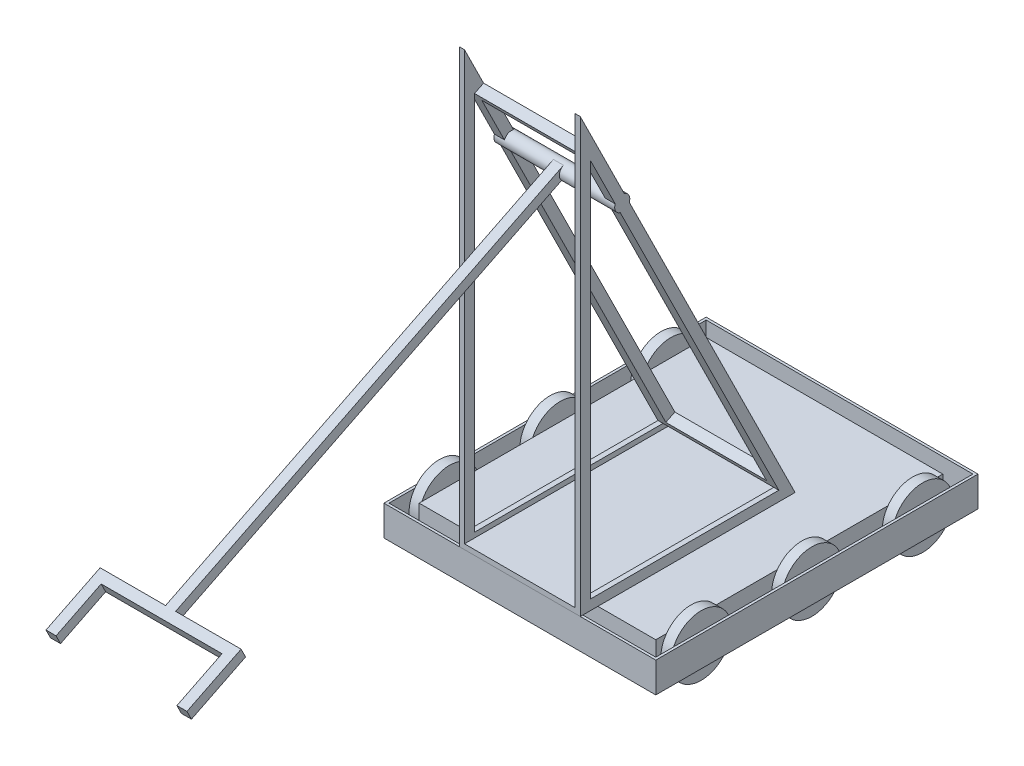
SolidWorks part; units mm, degrees
ref_plane "Front Plane" through (0, 0, 0) normal (0, 0, 1) x (1, 0, 0)
ref_plane "Top Plane" through (0, 0, 0) normal (0, 1, 0) x (1, 0, 0)
ref_plane "Right Plane" through (0, 0, 0) normal (1, 0, 0) x (0, 0, -1)
sketch "Sketch3" plane through (0, 0, 0) normal (0, 1, 0) x (1, 0, 0)
  line L5 (-342.9, -406.4) -> (342.9, -406.4)
  line L6 (-342.9, -406.4) -> (-342.9, 406.4)
  line L7 (-342.9, 406.4) -> (342.9, 406.4)
  line L8 (342.9, -406.4) -> (342.9, 406.4)
  line L9 (-342.9, -406.4) -> (342.9, 406.4) construction
  line L10 (-342.9, 406.4) -> (342.9, -406.4) construction
  point P0 (0, 0)
  dimension "D1" = 812.8
  dimension "D2" = 685.8
extrude "Extrude-Thin1" add sketch "Sketch3" along normal blind 76.2 thin contours L6 L7 L8 L5 thin type one direction reverse wall 6.35
sketch "Sketch5" plane through (0, 0, 0) normal (0, 1, 0) x (1, 0, 0)
  line L8 (-292.1, -355.6) -> (292.1, -355.6)
  line L9 (292.1, -355.6) -> (292.1, 355.6)
  line L10 (292.1, 355.6) -> (-292.1, 355.6)
  line L11 (-292.1, 355.6) -> (-292.1, -355.6)
  line L12 (-292.1, -355.6) -> (292.1, -355.6)
  line L13 (292.1, -355.6) -> (292.1, 355.6)
  line L14 (292.1, 355.6) -> (-292.1, 355.6)
  line L15 (-292.1, 355.6) -> (-292.1, -355.6)
  dimension "D1" = 50.8
extrude "Extrude-Thin2" add sketch "Sketch5" along normal blind 76.2 separate body thin thin type one direction wall 6.35
sketch "Sketch6" plane through (-292.1, 0, 0) normal (1, 0, 0) x (0, 0, -1)
  line L0 (0, 83.82) -> (0, -83.82) construction
  line L1 (0, 76.2) -> (0, 0) construction
  line L2 (355.6, 76.2) -> (-355.6, 76.2) construction
  line L3 (355.6, 0) -> (-355.6, 0) construction
  circle A0 centre (0, 38.1) radius 76.2
  circle A1 centre (-279.4, 38.1) radius 76.2
  circle A2 centre (279.4, 38.1) radius 76.2
  dimension "D1" = 152.4
  dimension "D2" = 152.4
  dimension "D5" = 152.4
  dimension "D3" = 279.4
  dimension "D4" = 279.4
extrude "Boss-Extrude2" add sketch "Sketch6" along direction (1, 0, 0) on the side against the normal offset from surface (25.4 mm away) 6.35 from offset 12.7 separate body up to face at (-336.55, 38.1, 0) offset against normal yes
extrude "Boss-Extrude3" add sketch "Sketch6<2>" along direction (-1, 0, 0) on the side against the normal offset from surface (25.4 mm away) 31.75 from offset 622.3 separate body up to face at (336.55, 38.1, 0) offset beyond the face yes
sketch "Sketch6<2>" plane through (-292.1, 0, 0) normal (1, 0, 0) x (0, 0, -1) same geometry as "Sketch6"
sketch "Sketch10" plane through (-292.1, 0, 0) normal (1, 0, 0) x (0, 0, -1)
  line L0 (-355.6, 76.2) -> (355.6, 76.2)
extrude "Extrude-Thin3" add sketch "Sketch10" along normal up to surface (584.2 mm away) thin up to face at (292.1, 38.1, 0) thin type one direction wall 6.35
sketch "Sketch11" plane through (0, 0, 0) normal (1, 0, 0) x (0, 0, -1)
  line L0 (-406.4, 76.2) -> (-406.4, 1168.4)
  line L1 (-406.4, 1168.4) -> (135.4005, 76.2)
  line L2 (-406.4, 76.2) -> (406.4, 76.2) construction
  line L3 (135.4005, 76.2) -> (-406.4, 76.2)
  dimension "D1" = 1092.2
  dimension "D2" = 1219.2
extrude "Extrude-Thin4" add sketch "Sketch11" along normal mid plane 304.8 separate body thin thin type one direction reverse wall 25.4
shell "Shell2" thickness 12.7 removed face at (0, 622.3, 135.4997) removed face at (0, 101.6, 143.2765) removed face at (0, 580.8199, 143.2765) removed face at (0, 580.8199, 381) removed face at (0, 622.3, 406.4)
sketch "Sketch12" plane through (-139.7, 0, 0) normal (1, 0, 0) x (0, 0, -1)
  line L0 (-381, 1060.0399) -> (94.447, 101.6)
  line L1 (-381, 1060.0399) -> (-358.2458, 1071.3274)
  line L2 (94.447, 101.6) -> (117.2012, 112.8875)
  line L3 (-358.2458, 1071.3274) -> (117.2012, 112.8875)
  line L4 (129.1005, 88.9) -> (-406.4, 1168.4) construction
extrude "Boss-Extrude4" add sketch "Sketch12" along normal up to surface (279.4 mm away) separate body up to face at (139.7, 448.7333, 227.8998)
shell "Shell3" thickness 12.7 removed face at (0, 580.8199, 143.2765) removed face at (0, 592.1075, 120.5223)
sketch "Sketch13" plane through (0, 0, 0) normal (1, 0, 0) x (0, 0, -1)
  line L0 (-311.9034, 920.75) -> (-289.1492, 932.0375) construction
  line L1 (94.447, 101.6) -> (-381, 1060.0399) construction
  line L2 (135.4005, 76.2) -> (-406.4, 1168.4) construction
  circle A0 centre (-300.5263, 926.3938) radius 19.05
  point P13 (-300.5263, 926.3938)
  dimension "D1" = 38.1
  dimension "D2" = 914.4
extrude "Boss-Extrude5" add sketch "Sketch13" along normal mid plane 304.8
ref_plane "Plane1" through (0, 880.1521, 436.6113) normal (0, 0.8958, 0.4444) x (1, 0, 0)
sketch "Sketch14" plane through (0, 880.1521, 436.6113) normal (0, 0.8958, 0.4444) x (1, 0, 0)
  line L0 (-12.7, 142.4588) -> (12.7, 142.4588)
  line L1 (12.7, 142.4588) -> (12.7, -949.7412)
  line L2 (12.7, -949.7412) -> (177.8, -949.7412)
  line L3 (177.8, -949.7412) -> (177.8, -1102.1412)
  line L4 (177.8, -1102.1412) -> (152.4, -1102.1412)
  line L5 (152.4, -1102.1412) -> (152.4, -975.1412)
  line L6 (152.4, -975.1412) -> (-152.4, -975.1412)
  line L7 (-152.4, -975.1412) -> (-152.4, -1102.1412)
  line L8 (-152.4, -1102.1412) -> (-177.8, -1102.1412)
  line L9 (-177.8, -1102.1412) -> (-177.8, -949.7412)
  line L10 (-177.8, -949.7412) -> (-12.7, -949.7412)
  line L11 (-12.7, -949.7412) -> (-12.7, 142.4588)
  line L12 (-127, 129.7588) -> (-127, 155.1588) construction
  line L13 (0, -447.04) -> (0, 447.04) construction
  point P14 (-127, 142.4588)
  point P17 (0, 142.4588)
  dimension "D1" = 25.4
  dimension "D2" = 1092.2
  dimension "D3" = 304.8
  dimension "D4" = 25.4
  dimension "D5" = 25.4
  dimension "D6" = 25.4
  dimension "D7" = 152.4
extrude "Boss-Extrude6" add sketch "Sketch14" against normal blind 25.4
